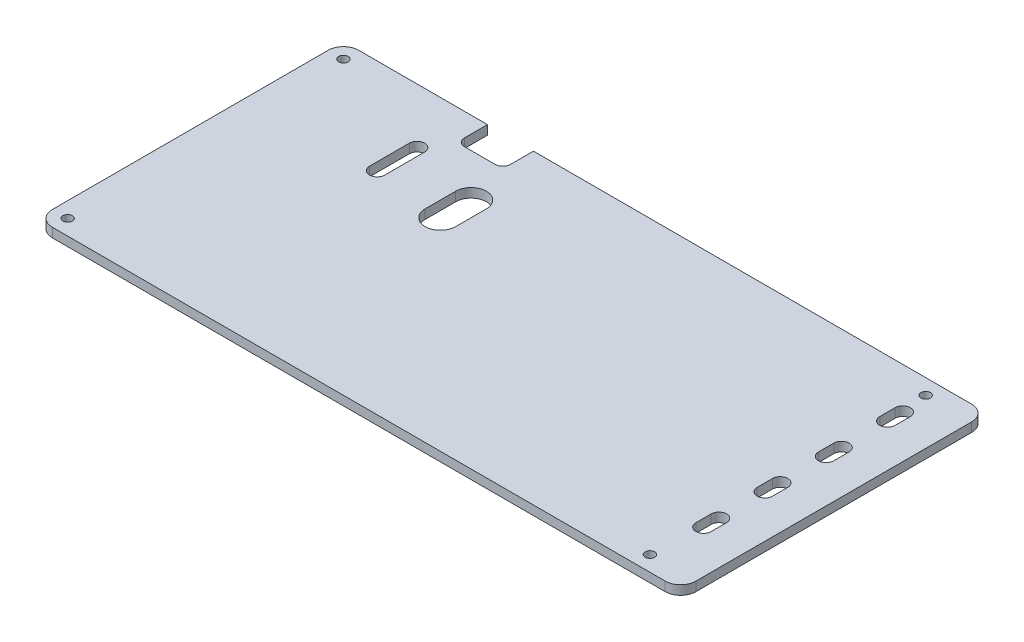
SolidWorks part; units mm, degrees
ref_plane "Front Plane" through (0, 0, 0) normal (0, 0, 1) x (1, 0, 0)
ref_plane "Top Plane" through (0, 0, 0) normal (0, 1, 0) x (1, 0, 0)
ref_plane "Right Plane" through (0, 0, 0) normal (1, 0, 0) x (0, 0, -1)
sketch "Sketch1" plane through (0, 0, 0) normal (0, 1, 0) x (1, 0, 0)
  line L1 (-105, 50) -> (105, 50)
  line L2 (-105, 50) -> (-105, -50)
  line L3 (-105, -50) -> (105, -50)
  line L4 (105, 50) -> (105, -50)
  line L5 (-105, 50) -> (105, -50) construction
  line L6 (-105, -50) -> (105, 50) construction
  point P0 (0, 0)
  dimension "D1" = 210
  dimension "D2" = 100
extrude "Boss-Extrude1" add sketch "Sketch1" along normal blind 3 contours L1 L4 L3 L2
sketch "Sketch2" plane through (0, 3, 0) normal (0, 1, 0) x (1, 0, 0)
  line L0 (-105, 50) -> (105, 50) construction
  line L1 (-105, 50) -> (-105, -50) construction
  line L2 (-105, -50) -> (105, -50) construction
  line L3 (105, 50) -> (105, -50) construction
  circle A0 centre (-100, 45) radius 1.55
  circle A1 centre (-100, -45) radius 1.55
  circle A2 centre (90, 45) radius 1.55
  circle A3 centre (90, -45) radius 1.55
  dimension "D3" = 3.1
  dimension "D4" = 3.1
  dimension "D5" = 3.1
  dimension "D6" = 3.1
  dimension "D1" = 5
  dimension "D2" = 5
  dimension "D7" = 5
  dimension "D8" = 5
  dimension "D9" = 5
  dimension "D10" = 15
  dimension "D11" = 15
  dimension "D12" = 5
extrude "Cut-Extrude1" cut sketch "Sketch2" against normal through all
fillet "Fillet1" radius 5 4 edges at (-105, 1.5, -50) (105, 1.5, -50) (105, 1.5, 50) (-105, 1.5, 50)
sketch "Sketch3" plane through (0, 3, 0) normal (0, 1, 0) x (1, 0, 0)
  line L0 (91, 50) -> (91, -50) construction
  line L5 (-100, 50) -> (100, 50) construction
  line L6 (-100, -50) -> (100, -50) construction
  line L7 (91, 36.5) -> (91, 31.5) construction
  line L12 (-63, 32) -> (-63, 19) construction
  line L13 (-60.5, 32) -> (-60.5, 19)
  line L18 (-39.365, 26) -> (-39.365, 16) construction
  line L19 (-34.365, 26) -> (-34.365, 16)
  line L20 (-65.5, 32) -> (-65.5, 19)
  line L21 (-105, 45) -> (-105, -45) construction
  line L22 (-44.365, 26) -> (-44.365, 16)
  line L23 (-58, 40) -> (-43, 40)
  line L24 (-58, 40) -> (-58, 50)
  line L25 (-58, 50) -> (-43, 50)
  line L26 (-43, 40) -> (-43, 50)
  line L27 (-58, 40) -> (-43, 50) construction
  line L28 (-58, 50) -> (-43, 40) construction
  line L29 (93.5, 36.5) -> (93.5, 31.5)
  line L30 (88.5, 36.5) -> (88.5, 31.5)
  line L31 (91, 16.5) -> (91, 11.5) construction
  line L32 (93.5, 16.5) -> (93.5, 11.5)
  line L33 (88.5, 16.5) -> (88.5, 11.5)
  line L34 (91, -3.5) -> (91, -8.5) construction
  line L35 (93.5, -3.5) -> (93.5, -8.5)
  line L36 (88.5, -3.5) -> (88.5, -8.5)
  line L37 (91, -23.5) -> (91, -28.5) construction
  line L38 (93.5, -23.5) -> (93.5, -28.5)
  line L39 (88.5, -23.5) -> (88.5, -28.5)
  arc A2 (-60.5, 32) -> (-65.5, 32) centre (-63, 32) ccw
  arc A3 (-65.5, 19) -> (-60.5, 19) centre (-63, 19) ccw
  arc A4 (-34.365, 26) -> (-44.365, 26) centre (-39.365, 26) ccw
  arc A5 (-44.365, 16) -> (-34.365, 16) centre (-39.365, 16) ccw
  arc A6 (93.5, 36.5) -> (88.5, 36.5) centre (91, 36.5) ccw
  arc A7 (88.5, 31.5) -> (93.5, 31.5) centre (91, 31.5) ccw
  arc A8 (93.5, 16.5) -> (88.5, 16.5) centre (91, 16.5) ccw
  arc A9 (88.5, 11.5) -> (93.5, 11.5) centre (91, 11.5) ccw
  arc A10 (93.5, -3.5) -> (88.5, -3.5) centre (91, -3.5) ccw
  arc A11 (88.5, -8.5) -> (93.5, -8.5) centre (91, -8.5) ccw
  arc A12 (93.5, -23.5) -> (88.5, -23.5) centre (91, -23.5) ccw
  arc A13 (88.5, -28.5) -> (93.5, -28.5) centre (91, -28.5) ccw
  point P4 (91, 34)
  point P12 (-63, 25.5)
  point P17 (-39.365, 21)
  point P26 (-50.5, 45)
  point P35 (91, 14)
  point P42 (91, -6)
  point P49 (91, -26)
  point P55 (0, 0)
  point P56 (0, 0)
  dimension "D2" = 196
  dimension "D3" = 5
  dimension "D4" = 42
  dimension "D5" = 75.5
  dimension "D6" = 5
  dimension "D7" = 13
  dimension "D8" = 65.635
  dimension "D9" = 71
  dimension "D10" = 10
  dimension "D11" = 10
  dimension "D12" = 10
  dimension "D13" = 54.5
  dimension "D14" = 15
  dimension "D15" = 5
  dimension "D16" = 5
  dimension "D17" = 5
  dimension "D18" = 24
  dimension "D19" = 44
  dimension "D20" = 64
  dimension "D21" = 84
  dimension "D22" = 5
  dimension "D23" = 5
  dimension "D24" = 5
  dimension "D25" = 5
extrude "Cut-Extrude2" cut sketch "Sketch3" against normal through all
fillet "Fillet2" radius 2.5 2 edges at (-43, 1.5, -40) (-58, 1.5, -40)
